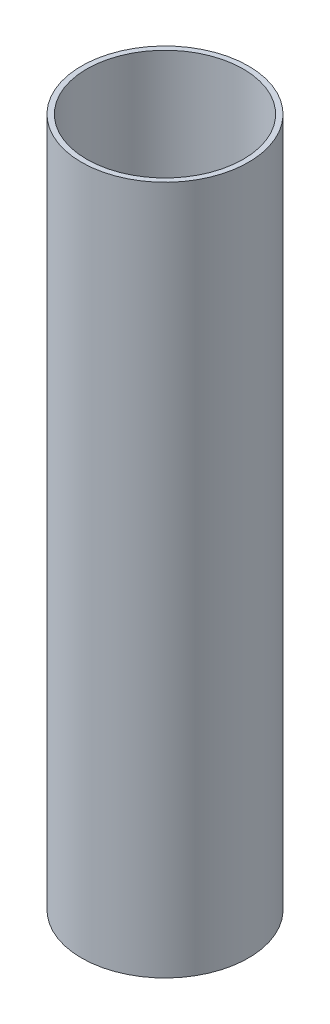
SolidWorks part; units mm, degrees
material "Silicon Dioxide"
ref_plane "Front Plane" through (0, 0, 0) normal (0, 0, 1) x (1, 0, 0)
ref_plane "Top Plane" through (0, 0, 0) normal (0, 1, 0) x (1, 0, 0)
ref_plane "Right Plane" through (0, 0, 0) normal (1, 0, 0) x (0, 0, -1)
sketch "Sketch1" plane through (0, 0, 0) normal (0, 1, 0) x (1, 0, 0)
  circle A0 centre (0, 0) radius 37.5
  circle A1 centre (0, 0) radius 40
  dimension "D1" = 80
  dimension "D2" = 75
extrude "Boss-Extrude1" add sketch "Sketch1" along normal blind 330.2
